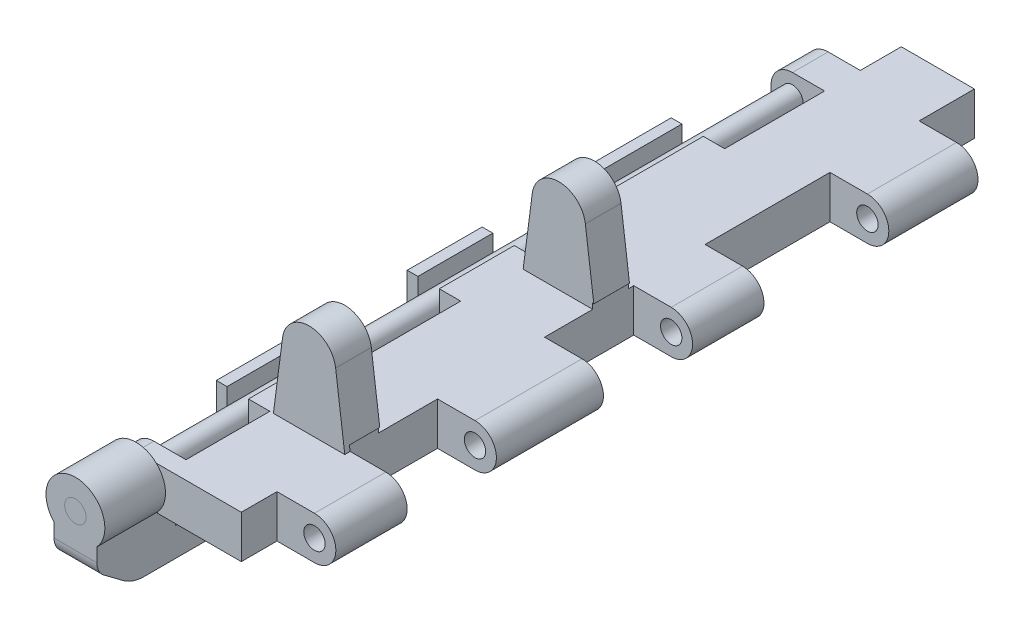
SolidWorks part; units mm, degrees
ref_plane "前视基准面" through (0, 0, 0) normal (0, 0, 1) x (1, 0, 0)
ref_plane "上视基准面" through (0, 0, 0) normal (0, 1, 0) x (1, 0, 0)
ref_plane "右视基准面" through (0, 0, 0) normal (1, 0, 0) x (0, 0, -1)
sketch "草图1" plane through (0, 0, 0) normal (0, 0, 1) x (1, 0, 0)
  line L0 (-1.2, 1.2) -> (-1.2, -3.9)
  line L1 (-1.2, -3.9) -> (1.2, -3.9)
  line L2 (0, -6.7644) -> (0, 6.7644) construction
  line L3 (1.2, -1.2) -> (1.2, -3.9)
  line L4 (-1.2, 1.2) -> (8, 1.2)
  line L5 (7.0675, 0) -> (-7.0675, 0) construction
  line L6 (1.2, -1.2) -> (8, -1.2)
  line L7 (4, 7.6444) -> (4, -4.6545) construction
  line L8 (2.5125, 5.1433) -> (2, 1.2)
  line L9 (5.4875, 5.1433) -> (6, 1.2)
  line L10 (0, 0) -> (8, 0) construction
  circle A0 centre (0, 0) radius 0.6
  circle A2 centre (8, 0) radius 1.2
  circle A3 centre (8, 0) radius 0.6
  circle A4 centre (4, 4.95) radius 1.5
  point P11 (0, -3.9)
  dimension "D1" = 1.2
  dimension "D5" = 2.4
  dimension "D6" = 1.2
  dimension "D10" = 3
  dimension "D4" = 1.2
  dimension "D7" = 8
  dimension "D8" = 4
  dimension "D9" = 3.75
  dimension "D11" = 2
extrude "凸台-拉伸1" add sketch "草图1" against normal blind 41.1 contours L0 L1 L3 | A0 | L4 L7 L6 A2 | L7 L4 L6 | A4 L7 L4 L9 | L7 A4 L8 L4 | L7 A4 | A4 L7 | A2 A3 region at (2.3097, -0.6566, 0) region at (4, 2.5028, 0) region at (4, 4.95, 0) region at (8.8245, 0.8245, 0)
sketch "草图2" plane through (0, 0, 0) normal (1, 0, 0) x (0, 0, -1)
  line L0 (41.1, 6.45) -> (0, 6.45) construction
  line L1 (0, 6.45) -> (5.7, 6.45)
  line L2 (0, 6.45) -> (0, 1.2)
  line L3 (0, 1.2) -> (5.7, 1.2)
  line L4 (5.7, 6.45) -> (5.7, 1.2)
  line L5 (41.1, 1.2) -> (0, 1.2) construction
  line L7 (0, 5.1433) -> (0, 1.2) construction
  line L8 (7.7, 6.45) -> (19.7, 6.45)
  line L9 (7.7, 6.45) -> (7.7, 1.2)
  line L10 (7.7, 1.2) -> (19.7, 1.2)
  line L11 (19.7, 6.45) -> (19.7, 1.2)
  line L12 (21.7, 6.45) -> (41.1, 6.45)
  line L13 (21.7, 6.45) -> (21.7, 1.2)
  line L14 (21.7, 1.2) -> (41.1, 1.2)
  line L15 (41.1, 6.45) -> (41.1, 1.2)
  dimension "D2" = 5.7
  dimension "D3" = 2
  dimension "D4" = 2
  dimension "D5" = 12
extrude "切除-拉伸1" cut sketch "草图2" along normal mid plane 19.5
sketch "草图6" plane through (0, 0, 0) normal (1, 0, 0) x (0, 0, -1)
  line L1 (5.7, 1.2) -> (1, 1.2)
  line L2 (5.7, 1.2) -> (5.7, -2.3)
  line L3 (5.7, -2.3) -> (1, -2.3)
  line L4 (1, 1.2) -> (1, -2.3)
  line L6 (16.4, 1.2) -> (9.9, 1.2)
  line L7 (16.4, 1.2) -> (16.4, -2.3)
  line L8 (16.4, -2.3) -> (9.9, -2.3)
  line L9 (9.9, 1.2) -> (9.9, -2.3)
  line L10 (25.2, 1.2) -> (20.6, 1.2)
  line L11 (25.2, 1.2) -> (25.2, -2.3)
  line L12 (25.2, -2.3) -> (20.6, -2.3)
  line L13 (20.6, 1.2) -> (20.6, -2.3)
  line L14 (36.8, 1.2) -> (31.2, 1.2)
  line L15 (36.8, 1.2) -> (36.8, -2.3)
  line L16 (36.8, -2.3) -> (31.2, -2.3)
  line L17 (31.2, 1.2) -> (31.2, -2.3)
  line L18 (41.1, 1.2) -> (38.8, 1.2)
  line L19 (41.1, 1.2) -> (41.1, -2.3)
  line L20 (41.1, -2.3) -> (38.8, -2.3)
  line L21 (38.8, 1.2) -> (38.8, -2.3)
  dimension "D1" = 1
  dimension "D2" = 4.7
  dimension "D3" = 3.5
  dimension "D4" = 6.5
  dimension "D5" = 4.2
  dimension "D6" = 4.2
  dimension "D7" = 6
  dimension "D8" = 4.6
  dimension "D9" = 5.6
  dimension "D10" = 2
extrude "切除-拉伸4" cut sketch "草图6" along normal blind 3 from surface starting at face at (-1.2, -1.35, -20.55)
sketch "草图9" plane through (0, 0, 0) normal (0, 0, 1) x (1, 0, 0)
  line L0 (-1.2, 1.2) -> (-1.2, -3.9) construction
  line L1 (-1.2, 1.2) -> (8, 1.2) construction
  line L2 (-1.2, 1.2) -> (-1.2, 0)
  line L3 (-1.2, 1.2) -> (0, 1.2)
  circle A0 centre (0, 0) radius 1.2
  dimension "D1" = 2.4
extrude "切除-拉伸5" cut sketch "草图9" against normal blind 3 contours A0 L3 L2 region at (-0.932, 0.932, 0)
extrude "切除-拉伸6" cut sketch "草图9<3>" against normal blind 3 from surface contours A0 L3 L2 region at (-0.932, 0.932, 0) starting at face at (0.6, -0.7667, -36.8)
sketch "草图9<3>" plane through (0, 0, 0) normal (0, 0, 1) x (1, 0, 0) same geometry as "草图9"
sketch "草图11" plane through (0, 0, 0) normal (0, 0, 1) x (1, 0, 0)
  line L0 (-0.6, 0) -> (-0.6, 1.2)
  line L1 (1.8, 1.2) -> (-1.2, 1.2) construction
  line L2 (-0.6, 1.2) -> (0.6, 1.2)
  line L3 (0, 1.2) -> (8, 1.2) construction
  line L4 (0.6, 1.2) -> (0.6, 0)
  line L5 (0.6, 0) -> (-0.6, 0)
  circle A0 centre (0, 0) radius 0.6 construction
extrude "切除-拉伸7" cut sketch "草图11" against normal blind 27 from surface starting at face at (0.6, -0.7667, -5.7)
sketch "草图12" plane through (0, 0, 0) normal (1, 0, 0) x (0, 0, -1)
  line L0 (31.2, 1.2) -> (25.2, 1.2) construction
  line L1 (29.7, -7.2209) -> (26.7, -7.2209)
  line L2 (29.7, -7.2209) -> (29.7, -2.9)
  line L3 (29.7, -2.9) -> (26.7, -2.9)
  line L4 (26.7, -7.2209) -> (26.7, -2.9)
  line L5 (29.7, -7.2209) -> (26.7, -2.9) construction
  line L6 (29.7, -2.9) -> (26.7, -7.2209) construction
  line L7 (19.75, -7.2209) -> (17.25, -7.2209)
  line L8 (19.75, -7.2209) -> (19.75, -2.9)
  line L9 (19.75, -2.9) -> (17.25, -2.9)
  line L10 (17.25, -7.2209) -> (17.25, -2.9)
  line L11 (19.75, -7.2209) -> (17.25, -2.9) construction
  line L12 (19.75, -2.9) -> (17.25, -7.2209) construction
  line L13 (9.05, -7.2209) -> (6.55, -7.2209)
  line L14 (9.05, -7.2209) -> (9.05, -2.9)
  line L15 (9.05, -2.9) -> (6.55, -2.9)
  line L16 (6.55, -7.2209) -> (6.55, -2.9)
  line L17 (9.05, -7.2209) -> (6.55, -2.9) construction
  line L18 (9.05, -2.9) -> (6.55, -7.2209) construction
  line L19 (20.6, 1.2) -> (16.4, 1.2) construction
  line L20 (9.9, 1.2) -> (5.7, 1.2) construction
  line L21 (41.1, -3.9) -> (0, -3.9) construction
  point P0 (28.2, -5.0605)
  point P5 (18.5, -5.0605)
  point P10 (7.8, -5.0605)
  point P15 (28.2, -2.9)
  point P18 (28.2, 1.2)
  point P19 (18.5, 1.2)
  point P22 (18.5, -2.9)
  point P23 (7.8, -2.9)
  point P26 (7.8, 1.2)
  dimension "D1" = 3
  dimension "D2" = 2.5
  dimension "D3" = 2.5
  dimension "D4" = 1
extrude "切除-拉伸8" cut sketch "草图12" along normal mid plane 7
sketch "草图13" plane through (0, 0, 0) normal (0, 1, 0) x (1, 0, 0)
  line L0 (0, 0) -> (8, 0) construction
  line L1 (5.9, 0) -> (9.2, 0)
  line L2 (5.9, 0) -> (5.9, 2)
  line L3 (5.9, 2) -> (9.2, 2)
  line L4 (9.2, 0) -> (9.2, 2)
  line L5 (9.2, 0) -> (9.2, 41.1) construction
  line L6 (9.2, 41.1) -> (8, 41.1) construction
  line L7 (5.9, 6) -> (9.2, 6)
  line L8 (5.9, 6) -> (5.9, 11)
  line L9 (5.9, 11) -> (9.2, 11)
  line L10 (9.2, 6) -> (9.2, 11)
  line L11 (5.9, 17) -> (9.2, 17)
  line L12 (5.9, 17) -> (5.9, 22)
  line L13 (5.9, 22) -> (9.2, 22)
  line L14 (9.2, 17) -> (9.2, 22)
  line L15 (5.9, 26) -> (9.2, 26)
  line L16 (5.9, 26) -> (5.9, 33)
  line L17 (5.9, 33) -> (9.2, 33)
  line L18 (9.2, 26) -> (9.2, 33)
  line L19 (5.9, 38) -> (9.2, 38)
  line L20 (5.9, 38) -> (5.9, 41.1)
  line L21 (5.9, 41.1) -> (9.2, 41.1)
  line L22 (9.2, 38) -> (9.2, 41.1)
  dimension "D1" = 2
  dimension "D2" = 4
  dimension "D3" = 5
  dimension "D4" = 6
  dimension "D5" = 5
  dimension "D6" = 4
  dimension "D7" = 7
  dimension "D8" = 3.3
  dimension "D9" = 5
extrude "切除-拉伸9" cut sketch "草图13" against normal mid plane 3
sketch "草图14" plane through (0, 0, 0) normal (0, 0, 1) x (1, 0, 0)
  line L0 (-1.2, -1.1325) -> (-1.2, -3.9)
  line L1 (-1.2, 0) -> (-1.2, -3.9) construction
  line L2 (-1.2, -3.9) -> (1.2, -3.9)
  line L3 (1.2, -3.9) -> (1.2, -1.1325)
  circle A0 centre (0, 0) radius 0.6
  circle A1 centre (0, 0) radius 1.65
  dimension "D1" = 3.3
extrude "凸台-拉伸2" add sketch "草图14" along normal blind 3.4 contours A1 A0 | A1 L0 L2 L3 region at (0, -2.6904, 0) region at (-0.5921, 1.49, 0)
sketch "草图15" plane through (0, 0, 0) normal (1, 0, 0) x (0, 0, -1)
  line L0 (-1.9333, -3.5) -> (-3, -2.7)
  line L1 (6.55, -3.9) -> (-3.4, -3.9) construction
  line L2 (-3.4, -1.1325) -> (-3.4, -3.9) construction
  line L3 (-0.254, -3.9) -> (-0.7333, -3.9)
  line L4 (-3.4, -1.9) -> (-3.4, -1.3337)
  line L5 (-0.7333, -3.9) -> (-3.4, -3.9)
  line L6 (-3.4, -3.9) -> (-3.4, -1.9)
  arc A0 (-0.7333, -3.9) -> (-1.9333, -3.5) centre (-0.7333, -1.9) cw
  arc A1 (-3.4, -1.9) -> (-3, -2.7) centre (-2.4, -1.9) ccw
  dimension "D1" = 2
  dimension "D2" = 1
extrude "切除-拉伸10" cut sketch "草图15" along normal mid plane 3.4 contours A1 L6 L5 A0 L0 region at (0, -3.3883, 2.7069)
ref_plane "基准面1" through (0, 0, -28.2) normal (0, 0, 1) x (1, 0, 0)
sketch "草图17" plane through (0, 0, 0) normal (0, 0, 1) x (1, 0, 0)
  circle A0 centre (0, 0) radius 0.6 construction
  circle A1 centre (0, 0) radius 0.6
extrude "凸台-拉伸3" add sketch "草图17" along normal blind 3.4 and the other way blind 38.8 separate body
sketch "草图18" plane through (0, 0, 0) normal (0, 0, 1) x (1, 0, 0)
  line L0 (0, 0) -> (8, 0) construction
  line L1 (0, 0) -> (8, 0)
